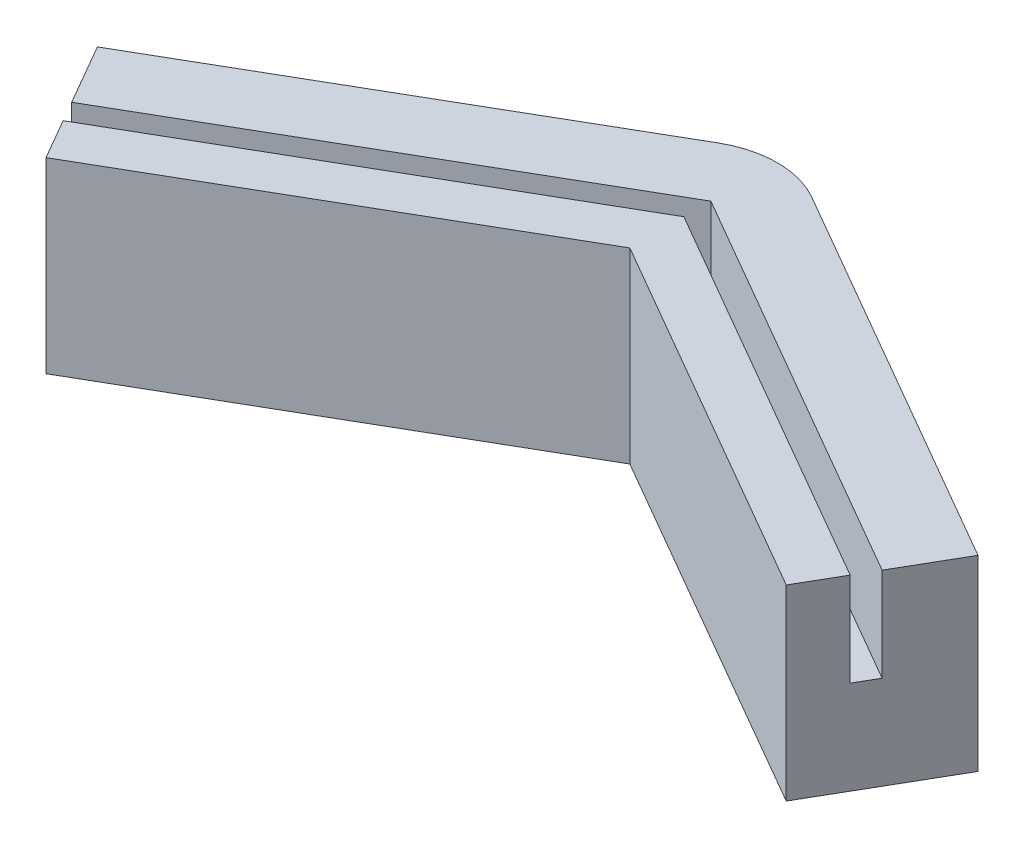
SolidWorks part; units mm, degrees
ref_plane "Front Plane" through (0, 0, 0) normal (0, 0, 1) x (1, 0, 0)
ref_plane "Top Plane" through (0, 0, 0) normal (0, 1, 0) x (1, 0, 0)
ref_plane "Right Plane" through (0, 0, 0) normal (1, 0, 0) x (0, 0, -1)
sketch "Sketch1" plane through (0, 0, 0) normal (0, 1, 0) x (1, 0, 0)
  line L0 (-91.3757, 0) -> (98.8396, 0) construction
  line L1 (0, -87.983) -> (0, 60.8417) construction
  line L2 (10, -5.7735) -> (94.1028, -54.3303)
  line L3 (-10, -5.7735) -> (-94.1028, -54.3303)
  line L4 (-94.1028, -54.3303) -> (-79.1028, -80.311)
  line L5 (-79.1028, -80.311) -> (0, -34.641)
  line L6 (0, -34.641) -> (79.1028, -80.311)
  line L7 (79.1028, -80.311) -> (94.1028, -54.3303)
  arc A0 (10, -5.7735) -> (-10, -5.7735) centre (0, -23.094) ccw
  point P13 (0, 0)
  dimension "D4" = 20
  dimension "D1" = 120
  dimension "D2" = 30
  dimension "D3" = 91.34
extrude "Boss-Extrude1" add sketch "Sketch1" along normal blind 40
sketch "Sketch2" plane through (0, 40, 0) normal (0, 1, 0) x (1, 0, 0)
  line L3 (-86.6028, -67.3206) -> (0, -17.3205)
  line L4 (0, -17.3205) -> (86.6028, -67.3206)
  line L5 (0, -23.094) -> (84.1028, -71.6508)
  line L6 (-84.1028, -71.6508) -> (0, -23.094)
  line L7 (0, -23.094) -> (84.1028, -71.6508)
  line L8 (-84.1028, -71.6508) -> (0, -23.094)
  line L9 (-84.1028, -71.6508) -> (-86.6028, -67.3206)
  line L10 (84.1028, -71.6508) -> (86.6028, -67.3206)
  dimension "D1" = 10
  dimension "D2" = 5
extrude "Cut-Extrude1" cut sketch "Sketch2" against normal blind 20
ref_axis "Axis1" through (0, 40, 34.641) along (1, 0, 0)
ref_plane "Plane1" through (0, -5.3158, 25.0088) normal (0, -0.2079, 0.9781) x (1, 0, 0)
